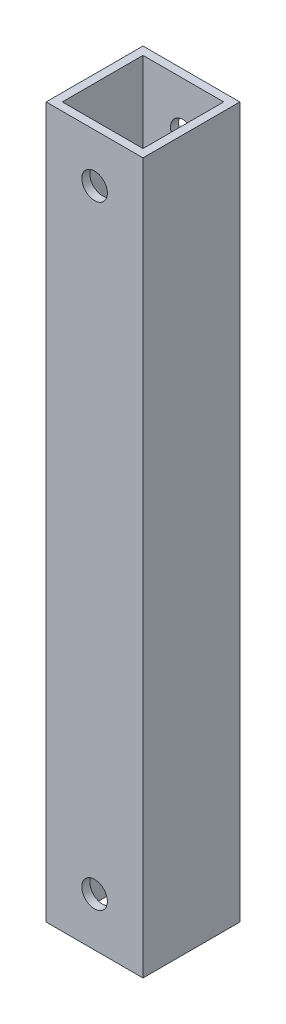
SolidWorks part; units mm, degrees
material "6061-T6 (SS)"
ref_plane "Front Plane" through (0, 0, 0) normal (0, 0, 1) x (1, 0, 0)
ref_plane "Top Plane" through (0, 0, 0) normal (0, 1, 0) x (1, 0, 0)
ref_plane "Right Plane" through (0, 0, 0) normal (1, 0, 0) x (0, 0, -1)
sketch "Sketch1" plane through (0, 0, 0) normal (0, 1, 0) x (1, 0, 0)
  line L0 (0, 19.05) -> (3.175, 19.05) construction
  line L1 (0, 0) -> (38.1, 0)
  line L2 (0, 0) -> (0, 38.1)
  line L3 (0, 38.1) -> (38.1, 38.1)
  line L4 (38.1, 0) -> (38.1, 38.1)
  line L5 (3.175, 3.175) -> (34.925, 3.175)
  line L6 (3.175, 3.175) -> (3.175, 34.925)
  line L7 (3.175, 34.925) -> (34.925, 34.925)
  line L8 (34.925, 3.175) -> (34.925, 34.925)
  line L9 (34.925, 19.05) -> (38.1, 19.05) construction
  line L10 (19.05, 3.175) -> (19.05, 0) construction
  line L11 (19.05, 34.925) -> (19.05, 38.1) construction
  dimension "D1" = 38.1
  dimension "D2" = 38.1
  dimension "D3" = 3.175
extrude "Boss-Extrude1" add sketch "Sketch1" along normal blind 279.4
hole_wizard "X (0.397) Diameter Hole1" positions "Sketch3" profile "Sketch2" hole size "X" standard "ANSI Inch" end condition through all
sketch "Sketch3" plane through (0, 0, 0) normal (0, 0, 1) x (1, 0, 0)
  line L0 (19.05, 0) -> (19.05, 19.05) construction
  line L1 (0, 0) -> (38.1, 0) construction
  line L2 (19.05, 19.05) -> (19.05, 260.35) construction
  line L3 (19.05, 260.35) -> (19.05, 279.4) construction
  line L4 (0, 279.4) -> (38.1, 279.4) construction
  point P0 (19.05, 260.35)
  point P2 (19.05, 19.05)
  dimension "D1" = 19.05
sketch "Sketch2" plane through (19.05, 260.35, 0) normal (1, 0, 0) x (0, -1, 0)
  line L0 (0, 0) -> (0, 38.1)
  line L1 (0, 38.1) -> (5.0419, 38.1)
  line L2 (5.0419, 38.1) -> (5.0419, 0)
  line L5 (5.0419, 0) -> (0, 0)
  line L11 (0, -6.35) -> (0, 107.95) construction
  dimension "Thru Hole Dia." = 10.0838
  dimension "Thru Hole Depth" = 38.1
